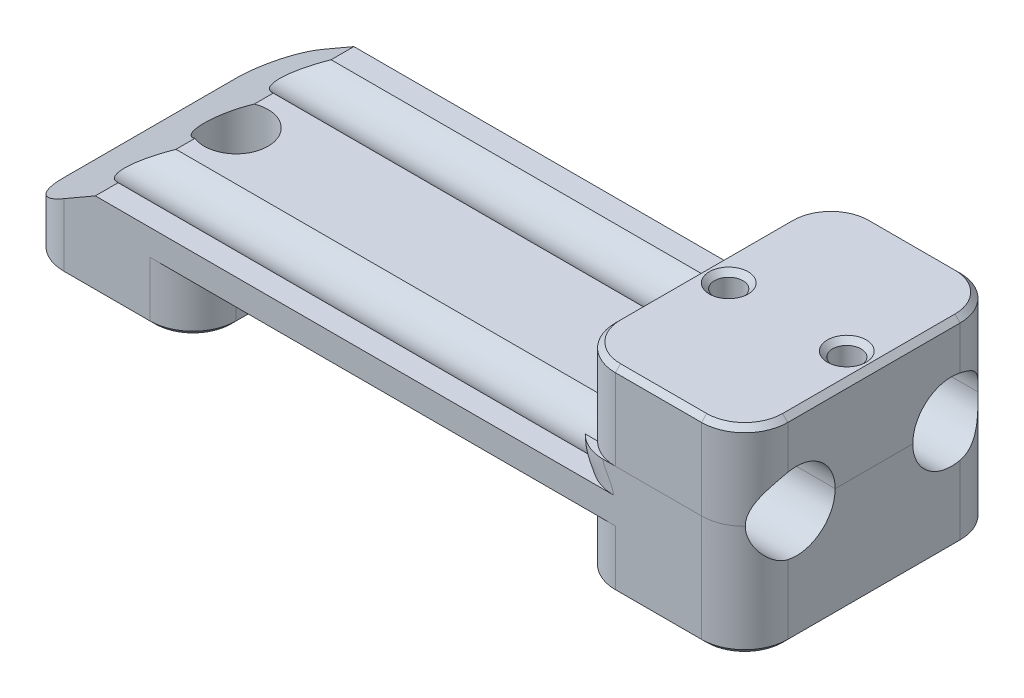
SolidWorks part; units mm, degrees
ref_plane "Front Plane" through (0, 0, 0) normal (0, 0, 1) x (1, 0, 0)
ref_plane "Top Plane" through (0, 0, 0) normal (0, 1, 0) x (1, 0, 0)
ref_plane "Right Plane" through (0, 0, 0) normal (1, 0, 0) x (0, 0, -1)
sketch "Sketch1" plane through (0, 0, 0) normal (0, 0, 1) x (1, 0, 0)
  line L0 (-64, 0) -> (-84, 0)
  line L1 (-84, 0) -> (-84, 5)
  line L2 (-75.3397, 10) -> (0, 10)
  line L3 (0, 10) -> (0, 0)
  line L4 (0, 0) -> (-20, 0)
  line L5 (-20, 0) -> (-20, 7)
  line L6 (-20, 7) -> (-64, 7)
  line L7 (-64, 7) -> (-64, 0)
  line L8 (-84, 5) -> (-75.3397, 10)
  line L10 (-64, 0) -> (-64, 7)
  line L11 (-64, 7) -> (-20, 7)
  dimension "D1" = 44
  dimension "D2" = 20
  dimension "D3" = 7
  dimension "D4" = 120
  dimension "D5" = 3
  dimension "D6" = 5
extrude "Boss-Extrude1" add sketch "Sketch1" along normal blind 30 contours L8 L1 L0 L7 L6 L5 L4 L3 L2 region at (-74, 0.8459, 0)
sketch "Sketch6" plane through (0, 0, 0) normal (1, 0, 0) x (0, 0, -1)
  line L1 (-30, 10) -> (0, 10)
  line L2 (-30, 10) -> (-30, 13)
  line L3 (-30, 13) -> (0, 13)
  line L4 (0, 10) -> (0, 13)
  dimension "D1" = 3
extrude "Boss-Extrude3" add sketch "Sketch6" against normal up to surface (20 mm away) up to face at (-20, 3.5, 15)
sketch "Sketch2" plane through (0, 0, 0) normal (0, -1, 0) x (1, 0, 0)
  line L0 (-84, 0) -> (-64, 30) construction
  line L1 (-20, 30) -> (0, 0) construction
  circle A0 centre (-10, 15) radius 3.7
  circle A1 centre (-10, 15) radius 2.2
  circle A2 centre (-74, 15) radius 3.7
  circle A3 centre (-74, 15) radius 2.2
  dimension "D1" = 4.4
  dimension "D2" = 7.4
extrude "Cut-Extrude1" cut sketch "Sketch2" against normal blind 45 contours A3 | A1
extrude "Cut-Extrude2" cut sketch "Sketch2<3>" against normal blind 45 from offset 4 offset against normal yes
sketch "Sketch2<3>" plane through (0, 0, 0) normal (0, -1, 0) x (1, 0, 0) same geometry as "Sketch2"
sketch "Sketch3" plane through (0, 0, 0) normal (1, 0, 0) x (0, 0, -1)
  line L0 (-24, 13) -> (-6, 13) construction
  line L1 (-15, 0) -> (-15, 13) construction
  line L2 (-30, 0) -> (0, 0) construction
  circle A0 centre (-24, 13) radius 4.5
  circle A1 centre (-6, 13) radius 4.5
  dimension "D1" = 9
  dimension "D2" = 18
  dimension "D3" = 6
extrude "Cut-Extrude3" cut sketch "Sketch3" against normal blind 146
sketch "Sketch5" plane through (0, 0, 0) normal (1, 0, 0) x (0, 0, -1)
  line L0 (0, 13) -> (0, 0) construction
  line L1 (-30, 13) -> (-28.5, 13)
  line L2 (-30, 13) -> (-30, 23)
  line L3 (-30, 23) -> (0, 23)
  line L4 (0, 13) -> (0, 23)
  line L5 (-19.5, 13) -> (-10.5, 13)
  line L6 (-1.5, 13) -> (0, 13)
  line L7 (-30, 13) -> (-30, 0) construction
  arc A0 (-19.5, 13) -> (-28.5, 13) centre (-24, 13) ccw
  arc A1 (-1.5, 13) -> (-10.5, 13) centre (-6, 13) ccw
  point P13 (-28.474, 10)
  point P18 (-0.5, 13)
  point P20 (-9.5, 13)
  point P22 (-29.165, 13)
  point P23 (-29.132, 13)
  point P25 (0, 0)
  point P26 (0, 0)
  point P27 (0, 0)
  point P30 (-20.5, 13)
  point P32 (-5, 12.3544)
  dimension "D2" = 4.5
  dimension "D3" = 4.5
  dimension "D1" = 10
extrude "Boss-Extrude2" add sketch "Sketch5" against normal blind 20 separate body
sketch "Sketch4" plane through (0, 13, 0) normal (0, 1, 0) x (1, 0, 0)
  line L1 (0, -10.5) -> (0, -19.5) construction
  line L5 (-10, -11.4771) -> (-10, -11.3) construction
  line L6 (-13.7, -15) -> (-20, -15) construction
  line L7 (-6.3, -15) -> (0, -15) construction
  line L9 (-13.7, -15) -> (-6.3, -15) construction
  circle A2 centre (-3.15, -15) radius 2.3
  circle A3 centre (-10, -15) radius 3.7 construction
  circle A4 centre (-10, -15) radius 3.7 construction
  circle A7 centre (-16.85, -15) radius 2.3
  circle A8 centre (-16.85, -15) radius 1.65
  circle A9 centre (-3.15, -15) radius 1.65
  point P4 (-10, -18.7)
  point P8 (-0.2788, -15.8948)
  point P9 (-2.8819, -15)
  point P14 (-10, -11.3)
  point P15 (-8.438, -18.3541)
  point P16 (0, 0)
  dimension "D1" = 3.3
  dimension "D2" = 4.6
  dimension "D3" = 4.6
extrude "Cut-Extrude4" cut sketch "Sketch4" against normal blind 7 contours A8 | A7 A8 | A2 A9 | A9 region at (-5.3849, 13, 15) region at (-19.0849, 13, 15) region at (-16.85, 13, 15) region at (-3.15, 13, 15)
extrude "Cut-Extrude6" cut sketch "Sketch4<4>" along normal blind 58 contours A8 | A9 region at (-16.85, 13, 15) region at (-3.15, 13, 15)
sketch "Sketch4<4>" plane through (0, 13, 0) normal (0, 1, 0) x (1, 0, 0) same geometry as "Sketch4"
fillet "Fillet1" radius 5 10 edges at (-20, 3.5, 0) (-64, 3.5, 0) (-84, 2.5, 0) (-84, 2.5, 30) (-64, 3.5, 30) (-20, 3.5, 30) (0, 6.5, 30) (0, 6.5, 0) (-20, 11.5, 0) (-20, 11.5, 30)
fillet "Fillet2" radius 5 4 edges at (-20, 18, 0) (-20, 18, 30) (0, 18, 30) (0, 18, 0)
chamfer "Chamfer1" distance 0.6 angle 45 18 edges at (-18.5355, 0, 28.5355) (-10, 0, 30) (-1.4645, 0, 28.5355) (0, 0, 15) (-1.4645, 0, 1.4645) (-10, 0, 0) (-18.5355, 0, 1.4645) (-20, 0, 15) (-10, 0, 12.8) (-82.5355, 0, 1.4645) (-84, 0, 15) (-82.5355, 0, 28.5355) (-74, 0, 30) (-65.4645, 0, 28.5355) (-64, 0, 15) (-65.4645, 0, 1.4645) (-74, 0, 0) (-74, 0, 12.8)
chamfer "Chamfer2" distance 0.6 angle 45 10 edges at (-1.4645, 23, 1.4645) (0, 23, 15) (-1.4645, 23, 28.5355) (-10, 23, 30) (-18.5355, 23, 28.5355) (-20, 23, 15) (-18.5355, 23, 1.4645) (-10, 23, 0) (-4.8, 23, 15) (-18.5, 23, 15)
